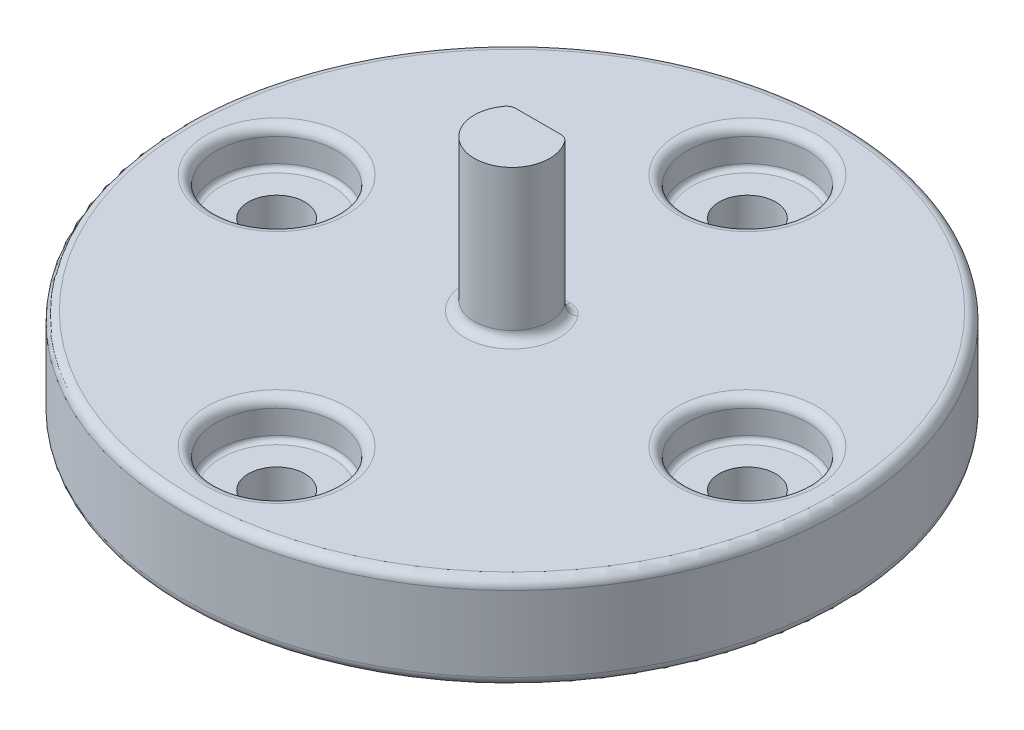
SolidWorks part; units mm, degrees
ref_plane "Front Plane" through (0, 0, 0) normal (0, 0, 1) x (1, 0, 0)
ref_plane "Top Plane" through (0, 0, 0) normal (0, 1, 0) x (1, 0, 0)
ref_plane "Right Plane" through (0, 0, 0) normal (1, 0, 0) x (0, 0, -1)
sketch "Sketch1" plane through (0, 0, 0) normal (0, 1, 0) x (1, 0, 0)
  line L0 (0, 0) -> (41.9723, 0) construction
  line L1 (41.9723, 0) -> (-40.3772, 0) construction
  line L2 (-30.1236, 1.4) -> (41.9723, 1.4) construction
  line L3 (0, 1.4) -> (41.9723, 1.4) construction
  line L5 (-1.4283, 1.4) -> (1.4283, 1.4)
  circle A0 centre (0, 0) radius 2 construction
  arc A2 (-1.4283, 1.4) -> (1.4283, 1.4) centre (0, 0) ccw
  dimension "D1" = 4
  dimension "D2" = 1.4
extrude "Boss-Extrude1" add sketch "Sketch1" along normal blind 8
fillet "Fillet1" radius 0.5 2 edges at (1.4283, 4, -1.4) (-1.4283, 4, -1.4)
sketch "Sketch2" plane through (0, 0, 0) normal (0, 1, 0) x (1, 0, 0)
  line L0 (0, 0) -> (-7.9491, 0) construction
  line L5 (-7.9491, 0) -> (8.8578, 0) construction
  line L6 (0, 0) -> (0, 5.3892) construction
  line L7 (0, 5.3892) -> (0, -6.4859) construction
  line L8 (0, 5) -> (-2.5, 5) construction
  line L9 (-2.5, 5) -> (3.5605, 5) construction
  line L10 (6, 0) -> (6, 4.7884) construction
  line L11 (6, 4.7884) -> (6, -5.905) construction
  line L12 (0, -5) -> (4.3483, -5) construction
  line L13 (4.3483, -5) -> (-5.4572, -5) construction
  line L14 (-6, 0) -> (-6, 3.5603) construction
  line L15 (-6, 3.5603) -> (-6, -6.8261) construction
  line L16 (2.5, 5) -> (2.5, 2.5) construction
  line L17 (2.5, 2.5) -> (6, 2.5) construction
  line L18 (6, -2.5) -> (2.5, -2.5) construction
  line L19 (2.5, -2.5) -> (2.5, -5) construction
  line L20 (-2.5, 5) -> (-2.5, 2.5) construction
  line L21 (-2.5, 2.5) -> (-6, 2.5) construction
  line L22 (-2.5, -5) -> (-2.5, -2.5) construction
  line L23 (-2.5, -2.5) -> (-6, -2.5) construction
  circle A0 centre (0, 5) radius 1.5 construction
  circle A1 centre (-6, 0) radius 1.5 construction
  circle A2 centre (6, 0) radius 1.5 construction
  circle A3 centre (0, -5) radius 1.5 construction
  circle A4 centre (0, 5) radius 2.5 construction
  circle A5 centre (-6, 0) radius 2.5 construction
  circle A6 centre (0, -5) radius 2.5 construction
  circle A7 centre (6, 0) radius 2.5 construction
  arc A8 (2.5, 5) -> (-2.5, 5) centre (0, 5) ccw construction
  arc A9 (6, -2.5) -> (6, 2.5) centre (6, 0) ccw construction
  arc A10 (2.5, -5) -> (-2.5, -5) centre (0, -5) cw construction
  arc A11 (-6, 2.5) -> (-6, -2.5) centre (-6, 0) ccw construction
  circle A12 centre (0, 0) radius 17.5
  circle A13 centre (0, 5) radius 4 construction
  circle A14 centre (6, 0) radius 4 construction
  point P0 (0, 0)
  dimension "D1" = 3
  dimension "D7" = 35
  dimension "D2" = 5
  dimension "D3" = 6
  dimension "D4" = 1
  dimension "D5" = 1.5
  dimension "D6" = 1.5
extrude "Boss-Extrude3" add sketch "Sketch2" against normal blind 5
sketch "Sketch3" plane through (0, -5, 0) normal (0, -1, 0) x (1, 0, 0)
  line L6 (0, 0) -> (-16.633, 0) construction
  line L7 (-16.633, 0) -> (19.5957, 0) construction
  line L8 (0, 0) -> (0, -13.6916) construction
  line L9 (0, -13.6916) -> (0, 14.9977) construction
  circle A3 centre (0, -5) radius 1.5 construction
  circle A4 centre (0, 12.5) radius 1.5
  circle A5 centre (12.5, 0) radius 1.5
  circle A6 centre (-12.5, 0) radius 1.5
  circle A12 centre (0, -12.5) radius 1.5
  dimension "D1" = 3
  dimension "D3" = 25
  dimension "D2" = 25
extrude "Cut-Extrude1" cut sketch "Sketch3" against normal through all both and the other way through all
sketch "Sketch4" plane through (0, 0, 0) normal (0, 1, 0) x (1, 0, 0)
  circle A12 centre (12.5, 0) radius 1.5 construction
  circle A13 centre (0, 12.5) radius 1.5 construction
  circle A14 centre (0, -12.5) radius 1.5 construction
  circle A15 centre (-12.5, 0) radius 1.5 construction
  circle A16 centre (12.5, 0) radius 1.5 construction
  circle A17 centre (0, 12.5) radius 1.5 construction
  circle A18 centre (0, -12.5) radius 1.5 construction
  circle A19 centre (-12.5, 0) radius 1.5 construction
  circle A20 centre (0, -12.5) radius 3.2
  circle A21 centre (0, 12.5) radius 3.2
  circle A22 centre (-12.5, 0) radius 3.2
  circle A23 centre (12.5, 0) radius 3.2
  dimension "D1" = 1.7
  dimension "D2" = 1.7
extrude "Cut-Extrude2" cut sketch "Sketch4" against normal offset from surface (2 mm away) 2 up to face at (0, 0, -11)
fillet "Fillet2" radius 0.5 4 edges at (0, 0, 15.7) (12.5, 0, 3.2) (0, 0, -9.3) (-12.5, 0, 3.2)
fillet "Fillet3" radius 0.25 4 edges at (12.5, -2, 3.2) (0, -2, 15.7) (0, -2, -9.3) (-12.5, -2, 3.2)
fillet "Fillet4" radius 0.5 2 edges at (0, -5, 17.5) (0, 0, 17.5)
fillet "Fillet5" radius 0.5 4 edges at (-1.4236, 0, -1.3472) (0, 0, -1.4) (1.4236, 0, -1.3472) (0, 0, 2)
